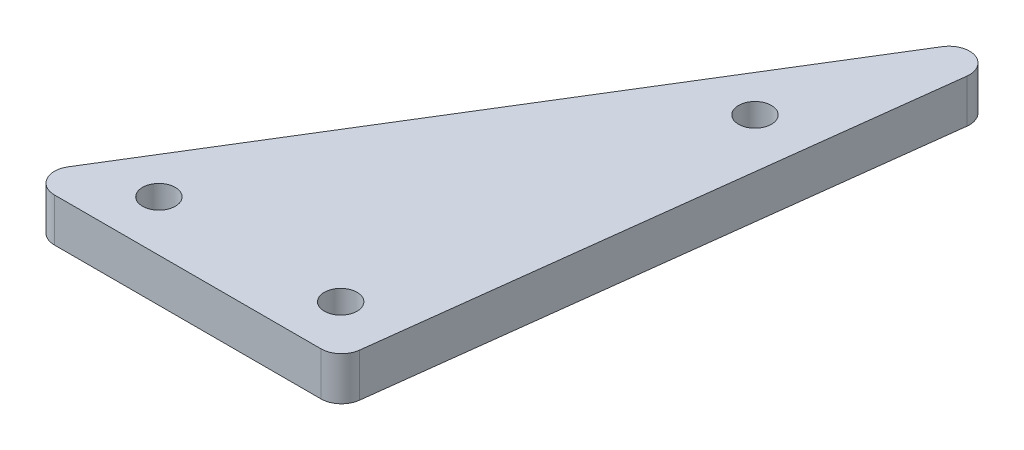
SolidWorks part; units mm, degrees
ref_plane "Front Plane" through (0, 0, 0) normal (0, 0, 1) x (1, 0, 0)
ref_plane "Top Plane" through (0, 0, 0) normal (0, 1, 0) x (1, 0, 0)
ref_plane "Right Plane" through (0, 0, 0) normal (1, 0, 0) x (0, 0, -1)
sketch "Sketch1" plane through (0, 0, 0) normal (0, 1, 0) x (1, 0, 0)
  line L0 (5.3684, 0) -> (44.3458, 0)
  line L1 (47.3235, 2.6344) -> (57.0401, 81.7704)
  line L2 (51.5075, 83.7081) -> (2.8134, 4.5722)
  arc A0 (44.3458, 0) -> (47.3235, 2.6344) centre (44.3458, 3) ccw
  arc A1 (5.3684, 0) -> (2.8134, 4.5722) centre (5.3684, 3) cw
  arc A2 (57.0401, 81.7704) -> (51.5075, 83.7081) centre (54.0625, 82.136) ccw
  point P6 (47, 0)
  point P9 (0, 0)
  dimension "D3" = 3
  dimension "D1" = 97
  dimension "D2" = 47
  dimension "D7" = 24.605
extrude "Boss-Extrude1" add sketch "Sketch1" along normal blind 6.35
sketch "Sketch2" plane through (0, 6.35, 0) normal (0, 1, 0) x (1, 0, 0)
  line L0 (8.9473, 5) -> (41.9473, 5) construction
  line L1 (41.9473, 5) -> (50.1739, 72) construction
  line L2 (50.1739, 72) -> (8.9473, 5) construction
  line L6 (5.3684, 0) -> (44.3458, 0) construction
  line L7 (51.5075, 83.7081) -> (2.8134, 4.5722) construction
  circle A0 centre (13.2421, 7.4) radius 2.4
  circle A1 centre (46.4506, 61.3694) radius 2.4
  circle A2 centre (39.824, 7.4) radius 2.4
  dimension "D6" = 4.8
  dimension "D7" = 4.8
  dimension "D8" = 4.8
  dimension "D1" = 33
  dimension "D2" = 67
  dimension "D3" = 97
  dimension "D4" = 5
  dimension "D5" = 5
extrude "Cut-Extrude1" cut sketch "Sketch2" against normal through all
